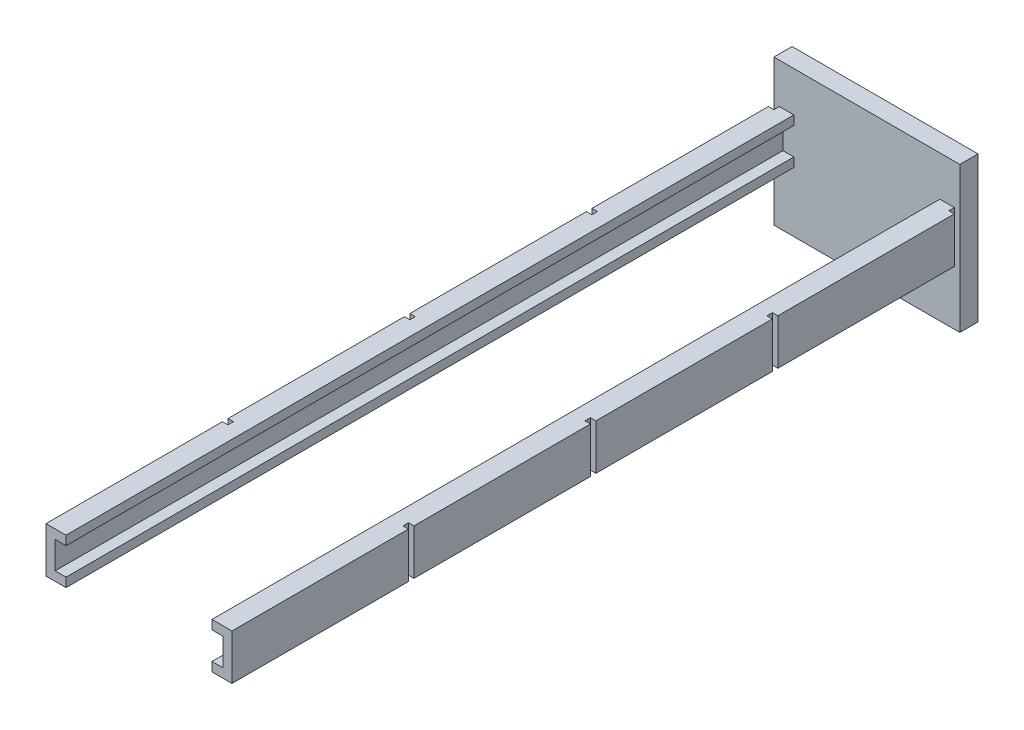
SolidWorks part; units mm, degrees
ref_plane "Plan de face" through (0, 0, 0) normal (0, 0, 1) x (1, 0, 0)
ref_plane "Plan de dessus" through (0, 0, 0) normal (0, 1, 0) x (1, 0, 0)
ref_plane "Plan de droite" through (0, 0, 0) normal (1, 0, 0) x (0, 0, -1)
sketch "Esquisse1" plane through (0, 0, 0) normal (0, 0, 1) x (1, 0, 0)
  line L0 (-40.1, -7.5) -> (-40.1, -12.5)
  line L1 (-40.1, 12.5) -> (-51.1, 12.5)
  line L2 (-40.1, 12.5) -> (-40.1, 7.5)
  line L3 (-40.1, -12.5) -> (-51.1, -12.5)
  line L4 (-51.1, 12.5) -> (-51.1, -12.5)
  line L5 (-40.1, -7.5) -> (-46.1, -7.5)
  line L6 (0, 0) -> (0, 26.5294) construction
  line L7 (-40.1, 7.5) -> (-46.1, 7.5)
  line L8 (-46.1, -7.5) -> (-46.1, 7.5)
  line L9 (51.1, 12.5) -> (51.1, -12.5)
  line L10 (40.1, 12.5) -> (51.1, 12.5)
  line L11 (40.1, 12.5) -> (40.1, 7.5)
  line L12 (40.1, 7.5) -> (46.1, 7.5)
  line L13 (46.1, -7.5) -> (46.1, 7.5)
  line L14 (40.1, -7.5) -> (46.1, -7.5)
  line L15 (40.1, -7.5) -> (40.1, -12.5)
  line L16 (40.1, -12.5) -> (51.1, -12.5)
  dimension "D1" = 6
  dimension "D2" = 15
  dimension "D3" = 5
  dimension "D4" = 5
  dimension "D5" = 5
  dimension "D6" = 7.5
  dimension "D7" = 40.1
extrude "Boss.-Extru.1" add sketch "Esquisse1" along normal blind 400
sketch "Esquisse2" plane through (0, 0, 0) normal (0, 0, -1) x (-1, 0, 0)
  line L0 (51.1, 12.5) -> (51.1, -12.5) construction
  line L1 (-51.1, 34.5585) -> (51.1, 34.5585)
  line L2 (-51.1, 34.5585) -> (-51.1, -45.4415)
  line L3 (-51.1, -45.4415) -> (51.1, -45.4415)
  line L4 (51.1, 34.5585) -> (51.1, -45.4415)
  line L5 (-51.1, -12.5) -> (-51.1, 12.5) construction
  dimension "D1" = 80
extrude "Boss.-Extru.2" add sketch "Esquisse2" along normal blind 10
sketch "Esquisse3" plane through (51.1, 0, 0) normal (1, 0, 0) x (0, 0, -1)
  line L0 (-400, 12.5) -> (0, 12.5) construction
  line L1 (0, -12.5) -> (-2.9913, -12.5)
  line L2 (0, -12.5) -> (0, 12.5)
  line L3 (0, 12.5) -> (-2.9913, 12.5)
  line L4 (-2.9913, -12.5) -> (-2.9913, 12.5)
extrude "Enlèv. mat.-Extru.1" cut sketch "Esquisse3" against normal blind 3
pattern_linear "Répétition linéaire1" count 4 spacing 100 along (0, 0, 1) of "Enlèv. mat.-Extru.1"
mirror "Symétrie1" about plane through (0, 0, 0) normal (1, 0, 0) of "Répétition linéaire1"
